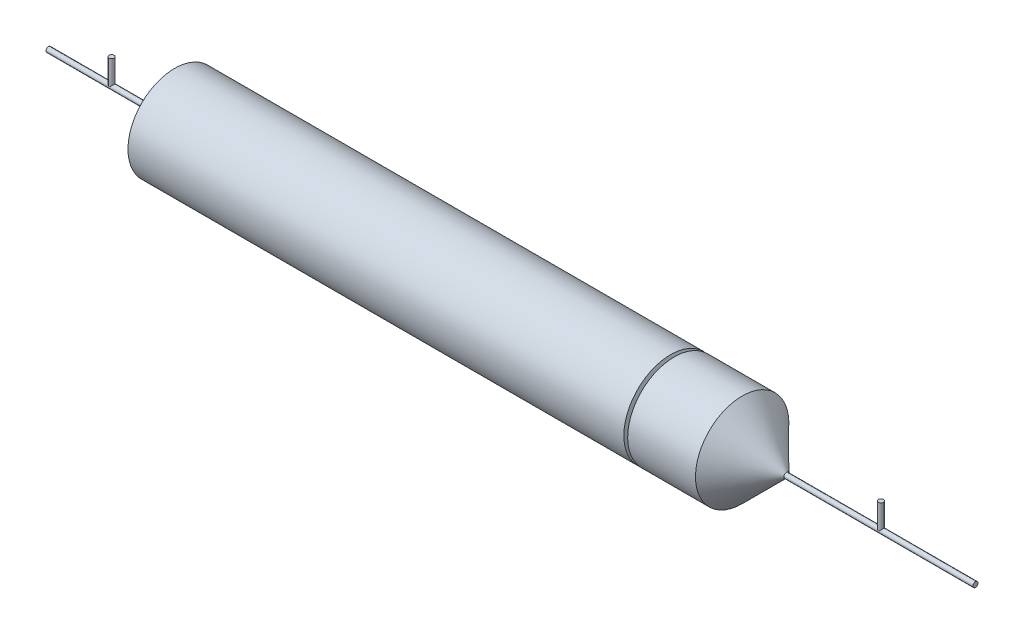
SolidWorks part; units mm, degrees
ref_plane "Front Plane" through (0, 0, 0) normal (0, 0, 1) x (1, 0, 0)
ref_plane "Top Plane" through (0, 0, 0) normal (0, 1, 0) x (1, 0, 0)
ref_plane "Right Plane" through (0, 0, 0) normal (1, 0, 0) x (0, 0, -1)
sketch "Sketch1" plane through (0, 0, 0) normal (0, 0, 1) x (1, 0, 0)
  line L1 (-225, 2) -> (-225, 37)
  line L3 (-225, 37) -> (225, 37)
  line L6 (-125, 0) -> (-325, 0)
  line L7 (-325, 0) -> (-325, 2)
  line L8 (-325, 2) -> (-225, 2)
  line L9 (-125, 0) -> (225, 0) construction
  line L10 (225, 37) -> (260, 2)
  line L11 (260, 2) -> (410, 2)
  line L12 (410, 2) -> (410, 0)
  line L13 (410, 0) -> (-125, 0)
  point P1 (0, 0)
  dimension "D2" = 450
  dimension "D3" = 200
  dimension "D4" = 2
  dimension "D6" = 2
  dimension "D7" = 150
revolve "Revolve1" add sketch "Sketch1" angle 360 about L9
sketch "Sketch2" plane through (0, 0, 0) normal (0, 1, 0) x (1, 0, 0)
  line L0 (-325, 0) -> (-275, 0)
  line L1 (-325, 2) -> (-325, -2) construction
  line L2 (260, 0) -> (335, 0)
  line L3 (260, -2) -> (260, 2) construction
  circle A0 centre (-275, 0) radius 2
  circle A1 centre (335, 0) radius 2
extrude "Boss-Extrude1" add sketch "Sketch2" along normal blind 20 contours A0 | A1
sketch "Sketch4" plane through (0, 0, 0) normal (0, 1, 0) x (1, 0, 0)
  line L0 (181.0319, 0) -> (181.0319, 10)
  line L1 (181.0319, 10) -> (171.2047, 37)
  line L2 (225, 37) -> (-225, 37) construction
  line L3 (178.0319, 0) -> (178.0319, 10)
  line L4 (178.0319, 10) -> (168.2047, 37)
  line L5 (168.2047, 37) -> (171.2047, 37)
  line L6 (178.0319, 0) -> (181.0319, 0)
  dimension "D1" = 10
  dimension "D2" = 0
  dimension "D3" = 160
  dimension "D4" = 160
  dimension "D5" = 3
  dimension "D6" = 10
revolve "Revolve2" add sketch "Sketch4" angle 360 about L6
sketch "Sketch5" plane through (178.0319, 0, 0) normal (-1, 0, 0) x (0, 0, 1)
  circle A0 centre (0, 0) radius 0.5
  point P19 (0, 0)
  dimension "D2" = 1
extrude "Cut-Extrude1" cut sketch "Sketch5" against normal blind 10
combine bodies "Combine1" operation type subtract main body 102 bodies to subtract 104
